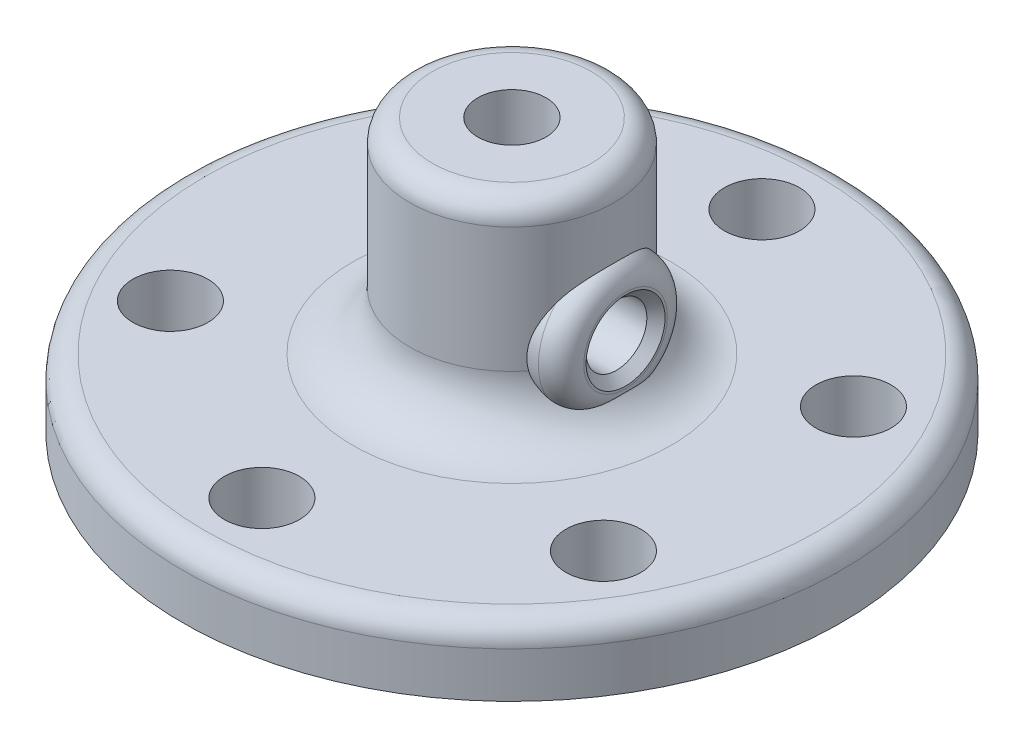
SolidWorks part; units mm, degrees
ref_plane "Front" through (0, 0, 0) normal (0, 0, 1) x (1, 0, 0)
ref_plane "Top" through (0, 0, 0) normal (0, 1, 0) x (1, 0, 0)
ref_plane "Right" through (0, 0, 0) normal (1, 0, 0) x (0, 0, -1)
sketch "Sketch1" plane through (0, 0, 0) normal (1, 0, 0) x (0, 0, -1)
  line L0 (0, 0) -> (0, 55.8941) construction
  line L1 (-3, 24) -> (-9, 24)
  line L2 (-9, 24) -> (-9, 6)
  line L3 (-9, 6) -> (-29, 6)
  line L4 (-29, 6) -> (-29, 0)
  line L5 (-29, 0) -> (-3.05, 0)
  line L7 (-3, 6) -> (-3, 24)
  line L8 (-3, 6) -> (0, 6)
  line L9 (0, 6) -> (0, 0)
  line L10 (0, 0) -> (-3.05, 0)
  dimension "D1" = 6
  dimension "D2" = 6
  dimension "D3" = 18
  dimension "D4" = 6
  dimension "D5" = 20
revolve "Revolve1" add sketch "Sketch1" angle 360 about L0
ref_plane "Plane1" through (10, 0, 0) normal (1, 0, 0) x (0, 0, -1)
sketch "Sketch2" plane through (10, 0, 0) normal (1, 0, 0) x (0, 0, -1)
  circle A0 centre (0, 12) radius 5.675
  circle A1 centre (0, 12) radius 2.675
  dimension "D1" = 6
  dimension "D2" = 3
  dimension "D3" = 5.35
extrude "Boss-Extrude1" add sketch "Sketch2" against normal up to next
sketch "Sketch3" plane through (10, 0, 0) normal (1, 0, 0) x (0, 0, -1)
  circle A0 centre (0, 12) radius 2.675 construction
  circle A1 centre (0, 12) radius 2.675
extrude "Cut-Extrude1" cut sketch "Sketch3" against normal up to next
fillet "Fillet1" radius 5 1 edges at (0, 6, -9)
fillet "Fillet3" radius 2 3 edges at (0, 24, -9) (10, 17.675, 0) (0, 6, -29)
chamfer "Chamfer2" distance 0.8 angle 45 1 edges at (10, 12, -2.675)
sketch "Sketch4" plane through (0, 0, 0) normal (0, -1, 0) x (1, 0, 0)
  circle A0 centre (0, 0) radius 6.45
  dimension "D1" = 12.9
extrude "Boss-Extrude2" add sketch "Sketch4" along normal blind 10
sketch "Sketch5" plane through (0, 0, 0) normal (0, -1, 0) x (1, 0, 0)
  circle A0 centre (0, 0) radius 6.45 construction
  circle A1 centre (0, 0) radius 29
  circle A2 centre (0, 0) radius 29
  circle A3 centre (0, 0) radius 6.45
  circle A4 centre (0, 0) radius 11.34
  circle M2 centre (0, 0) radius 6.45
  dimension "D2" = 4.89
  dimension "D1" = 0
extrude "Cut-Extrude2" cut sketch "Sketch5" against normal blind 2.1 contours A4 M2 region at (-11.0193, 0, 0)
chamfer "Chamfer3" distance 3.8 distance2 2 1 edges at (0, 0, -11.34) first distance on face at (0, 0, -11.34)
fillet "Fillet4" radius 1 2 edges at (0, 2, 11.34) (0, 2.1, -6.45)
sketch "Sketch6" plane through (0, 0, 0) normal (0, -1, 0) x (1, 0, 0)
  line L0 (0, 0) -> (-19.0526, -11) construction
  line L1 (0, 0) -> (-19.0526, 11) construction
  line L2 (0, 0) -> (0, 22) construction
  line L3 (0, 0) -> (19.0526, 11) construction
  line L4 (0, 0) -> (19.0526, -11) construction
  line L5 (0, 0) -> (0, -22) construction
  line L6 (0, 0) -> (19.3865, 0) construction
  circle A0 centre (19.0526, 11) radius 3.302
  circle A1 centre (19.0526, -11) radius 3.302
  circle A2 centre (0, -22) radius 3.302
  circle A3 centre (-19.0526, -11) radius 3.302
  circle A4 centre (-19.0526, 11) radius 3.302
  circle A5 centre (0, 22) radius 3.302
  point P10 (0, 0)
  dimension "D4" = 6.604
  dimension "D1" = 22
  dimension "D3" = 30
  dimension "D2" = 6
extrude "Cut-Extrude3" cut sketch "Sketch6" against normal through all
